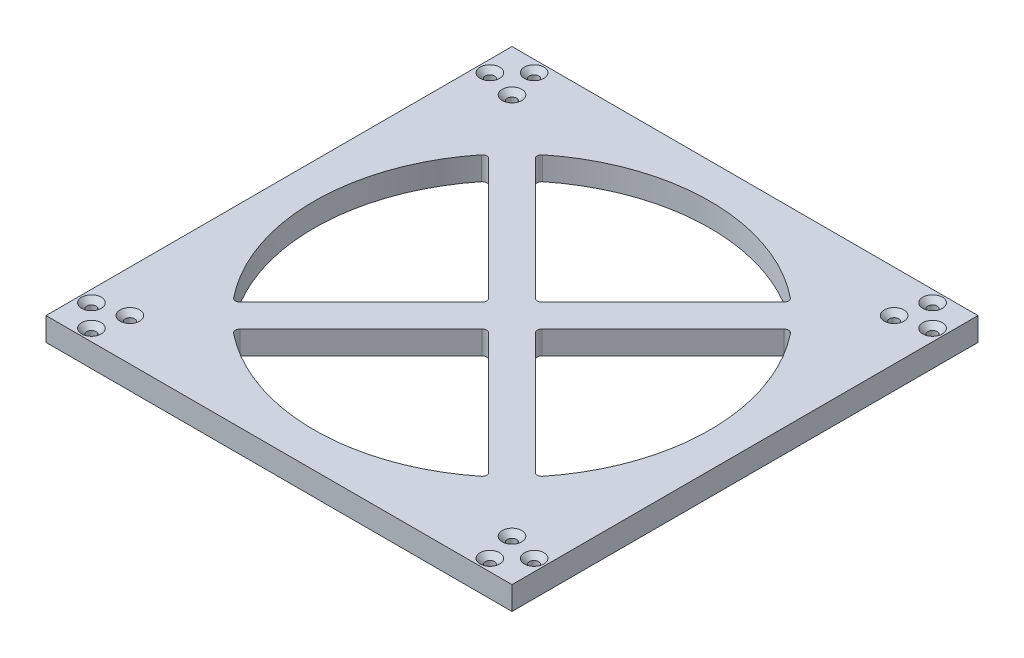
SolidWorks part; units mm, degrees
ref_plane "Front Plane" through (0, 0, 0) normal (0, 0, 1) x (1, 0, 0)
ref_plane "Top Plane" through (0, 0, 0) normal (0, 1, 0) x (1, 0, 0)
ref_plane "Right Plane" through (0, 0, 0) normal (1, 0, 0) x (0, 0, -1)
sketch "Sketch2" plane through (0, 0, 0) normal (0, 1, 0) x (1, 0, 0)
  line L0 (0, 50) -> (100, 50) construction
  line L1 (0, 0) -> (100, 0)
  line L2 (0, 0) -> (0, 100)
  line L3 (0, 100) -> (100, 100)
  line L4 (100, 0) -> (100, 100)
  line L5 (50, 0) -> (50, 100) construction
  line L14 (23.3308, 81.6692) -> (49.2929, 55.7071)
  line L15 (50.7071, 55.7071) -> (76.6692, 81.6692)
  line L16 (81.6692, 76.6692) -> (55.7071, 50.7071)
  line L17 (55.7071, 49.2929) -> (81.6692, 23.3308)
  line L18 (76.6692, 18.3308) -> (50.7071, 44.2929)
  line L19 (49.2929, 44.2929) -> (23.3308, 18.3308)
  line L20 (18.3308, 23.3308) -> (44.2929, 49.2929)
  line L21 (44.2929, 50.7071) -> (18.3308, 76.6692)
  arc A1 (76.5876, 83.1564) -> (23.4124, 83.1564) centre (50, 50) ccw
  arc A4 (49.2929, 55.7071) -> (50.7071, 55.7071) centre (50, 56.4142) ccw
  arc A5 (76.6692, 81.6692) -> (76.5876, 83.1564) centre (75.962, 82.3763) ccw
  arc A6 (23.3308, 81.6692) -> (23.4124, 83.1564) centre (24.038, 82.3763) cw
  arc A7 (83.1564, 23.4124) -> (83.1564, 76.5876) centre (50, 50) ccw
  arc A8 (55.7071, 50.7071) -> (55.7071, 49.2929) centre (56.4142, 50) ccw
  arc A9 (81.6692, 23.3308) -> (83.1564, 23.4124) centre (82.3763, 24.038) ccw
  arc A10 (81.6692, 76.6692) -> (83.1564, 76.5876) centre (82.3763, 75.962) cw
  arc A11 (23.4124, 16.8436) -> (76.5876, 16.8436) centre (50, 50) ccw
  arc A12 (50.7071, 44.2929) -> (49.2929, 44.2929) centre (50, 43.5858) ccw
  arc A13 (23.3308, 18.3308) -> (23.4124, 16.8436) centre (24.038, 17.6237) ccw
  arc A14 (76.6692, 18.3308) -> (76.5876, 16.8436) centre (75.962, 17.6237) cw
  arc A15 (16.8436, 76.5876) -> (16.8436, 23.4124) centre (50, 50) ccw
  arc A16 (44.2929, 49.2929) -> (44.2929, 50.7071) centre (43.5858, 50) ccw
  arc A17 (18.3308, 76.6692) -> (16.8436, 76.5876) centre (17.6237, 75.962) ccw
  arc A18 (18.3308, 23.3308) -> (16.8436, 23.4124) centre (17.6237, 24.038) cw
  point P16 (50, 55)
  point P50 (50, 50)
  dimension "D3" = 90
  dimension "D4" = 42.5
  dimension "D7" = 1
  dimension "D1" = 100
  dimension "D2" = 100
  dimension "D5" = 45
  dimension "D6" = 5
  dimension "D8" = 4
extrude "Boss-Extrude2" add sketch "Sketch2" along normal blind 5
sketch "Sketch3" plane through (0, 5, 0) normal (0, 1, 0) x (1, 0, 0)
  line L0 (0, 50) -> (100, 50) construction
  line L1 (0, 100) -> (0, 0) construction
  line L2 (100, 0) -> (100, 100) construction
  line L3 (50, 0) -> (50, 50) construction
  line L4 (0, 0) -> (100, 0) construction
  point P10 (9, 91)
  point P14 (91, 91)
  point P15 (91, 9)
  point P16 (9, 9)
  point P17 (50, 50)
  dimension "D1" = 41
  dimension "D2" = 41
  dimension "D3" = 4
hole_wizard "Tap Drill for M2x0.4 Tap1" positions "3DSketch1" profile "Sketch5" hole size "M2x0.4" standard "ANSI Metric" end condition through all
sketch3d "3DSketch1"
  point P0 (9, 5, -9)
  point P3 (9, 5, -91)
  point P6 (91, 5, -91)
  point P9 (91, 5, -9)
sketch "Sketch5" plane through (9, 5, -9) normal (1, 0, 0) x (0, 0, 1)
  line L0 (0, 0) -> (0, 5)
  line L1 (0, 5) -> (1, 5)
  line L2 (1, 5) -> (1, 1.1)
  line L3 (1, 1.1) -> (2.1, 0)
  line L5 (2.1, 0) -> (0, 0)
  line L6 (-1, 1.1) -> (-2.1, 0) construction
  line L11 (0, -6.35) -> (0, 107.95) construction
  dimension "Thru Hole Dia." = 2
  dimension "Thru Hole Depth" = 5
  dimension "Near C'Sink Dia." = 4.2
  dimension "Near C'Sink Angle" = 90
sketch "Sketch6" plane through (0, 5, 0) normal (0, 1, 0) x (1, 0, 0)
  line L0 (0, 0) -> (100, 0) construction
  line L1 (0, 100) -> (0, 0) construction
  point P0 (2.5, 7.25)
  point P5 (7.25, 2.5)
  dimension "D1" = 7.25
  dimension "D2" = 2.5
  dimension "D3" = 2.5
  dimension "D4" = 7.25
hole_wizard "Tap Drill for M2x0.4 Tap2" positions "3DSketch2" profile "Sketch8" hole size "M2x0.4" standard "ANSI Metric" end condition through all
sketch3d "3DSketch2"
  point P0 (2.5, 5, -7.25)
  point P3 (7.25, 5, -2.5)
sketch "Sketch8" plane through (2.5, 5, -7.25) normal (1, 0, 0) x (0, 0, 1)
  line L0 (0, 0) -> (0, 5)
  line L1 (0, 5) -> (1, 5)
  line L2 (1, 5) -> (1, 1.1)
  line L3 (1, 1.1) -> (2.1, 0)
  line L5 (2.1, 0) -> (0, 0)
  line L6 (-1, 1.1) -> (-2.1, 0) construction
  line L11 (0, -6.35) -> (0, 107.95) construction
  dimension "Thru Hole Dia." = 2
  dimension "Thru Hole Depth" = 5
  dimension "Near C'Sink Dia." = 4.2
  dimension "Near C'Sink Angle" = 90
ref_axis "Axis1" through (50, 5, -50) along (0, -1, 0)
pattern_circular "CirPattern1" count 4 over 360 about axis through (50, 5, -50) along (0, -1, 0) of "Tap Drill for M2x0.4 Tap2"
